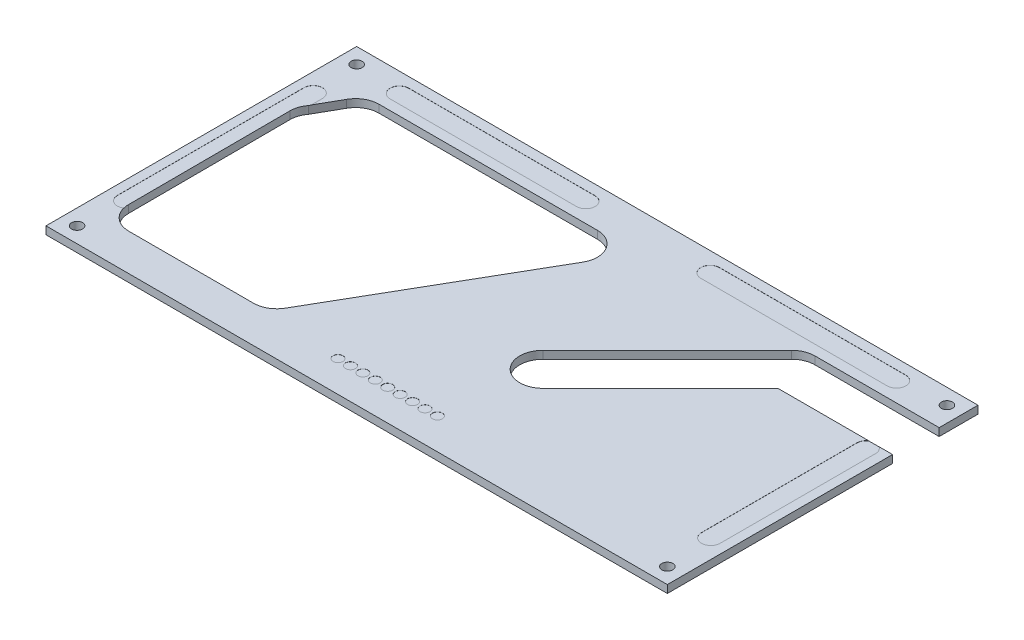
SolidWorks part; units mm, degrees
ref_plane "Front" through (0, 0, 0) normal (0, 0, 1) x (1, 0, 0)
ref_plane "Top" through (0, 0, 0) normal (0, 1, 0) x (1, 0, 0)
ref_plane "Right" through (0, 0, 0) normal (1, 0, 0) x (0, 0, -1)
sketch "Sketch1" plane through (0, 0, 0) normal (0, 1, 0) x (1, 0, 0)
  line L1 (0, 0) -> (127, 0)
  line L2 (0, 0) -> (0, 63.5)
  line L3 (0, 63.5) -> (127, 63.5)
  line L4 (127, 0) -> (127, 63.5)
  dimension "D1" = 63.5
  dimension "D2" = 127
extrude "Boss-Extrude1" add sketch "Sketch1" along normal blind 1.5875
sketch "Sketch2" plane through (0, 1.5875, 0) normal (0, 1, 0) x (1, 0, 0)
  line L0 (0, 63.5) -> (0, 0) construction
  line L1 (127, 63.5) -> (0, 63.5) construction
  line L2 (63.5, 63.5) -> (63.5, 0) construction
  line L3 (0, 0) -> (127, 0) construction
  circle A0 centre (3.175, 60.325) radius 1.1303
  circle A1 centre (3.175, 3.175) radius 1.1303
  circle A2 centre (123.825, 3.175) radius 1.1303
  circle A3 centre (123.825, 60.325) radius 1.1303
  dimension "D1" = 2.2606
  dimension "D2" = 3.175
  dimension "D3" = 3.175
  dimension "D4" = 2
extrude "Cut-Extrude1" cut sketch "Sketch2" against normal through all
sketch "Sketch3" plane through (0, 1.5875, 0) normal (0, 1, 0) x (1, 0, 0)
  line L0 (63.5, 63.5) -> (63.5, 0) construction
  line L1 (127, 63.5) -> (0, 63.5) construction
  line L2 (0, 0) -> (127, 0) construction
  line L3 (3.81, 50.8) -> (3.81, 12.7) construction
  line L4 (5.715, 50.8) -> (5.715, 12.7)
  line L5 (1.905, 50.8) -> (1.905, 12.7)
  line L6 (50.8, 59.5399) -> (12.7, 59.5399) construction
  line L7 (50.8, 57.6349) -> (12.7, 57.6349)
  line L8 (50.8, 61.4449) -> (12.7, 61.4449)
  line L9 (76.2, 59.5399) -> (114.3, 59.5399) construction
  line L10 (76.2, 57.6349) -> (114.3, 57.6349)
  line L11 (76.2, 61.4449) -> (114.3, 61.4449)
  line L12 (123.19, 44.45) -> (123.19, 12.7) construction
  line L13 (125.095, 44.45) -> (125.095, 12.7)
  line L14 (121.285, 44.45) -> (121.285, 12.7)
  circle A0 centre (63.5, 6.35) radius 1.016
  circle A1 centre (66.04, 6.35) radius 1.016
  circle A2 centre (68.58, 6.35) radius 1.016
  circle A3 centre (71.12, 6.35) radius 1.016
  circle A4 centre (73.66, 6.35) radius 1.016
  circle A5 centre (60.96, 6.35) radius 1.016
  circle A6 centre (58.42, 6.35) radius 1.016
  circle A7 centre (55.88, 6.35) radius 1.016
  circle A8 centre (53.34, 6.35) radius 1.016
  arc A9 (5.715, 50.8) -> (1.905, 50.8) centre (3.81, 50.8) ccw
  arc A10 (1.905, 12.7) -> (5.715, 12.7) centre (3.81, 12.7) ccw
  arc A11 (50.8, 57.6349) -> (50.8, 61.4449) centre (50.8, 59.5399) ccw
  arc A12 (12.7, 61.4449) -> (12.7, 57.6349) centre (12.7, 59.5399) ccw
  arc A13 (76.2, 57.6349) -> (76.2, 61.4449) centre (76.2, 59.5399) cw
  arc A14 (114.3, 61.4449) -> (114.3, 57.6349) centre (114.3, 59.5399) cw
  arc A15 (125.095, 44.45) -> (121.285, 44.45) centre (123.19, 44.45) ccw
  arc A16 (121.285, 12.7) -> (125.095, 12.7) centre (123.19, 12.7) ccw
  point P26 (3.81, 31.75)
  point P33 (31.75, 59.5399)
  point P40 (95.25, 59.5399)
  point P47 (123.19, 28.575)
  dimension "D2" = 2.032
  dimension "D1" = 57.15
  dimension "D5" = 3.81
  dimension "D6" = 59.69
  dimension "D7" = 12.7
  dimension "D8" = 38.1
  dimension "D9" = 3.81
  dimension "D10" = 38.1
  dimension "D11" = 50.8
  dimension "D12" = 3.81
  dimension "D13" = 59.69
  dimension "D14" = 31.75
  dimension "D15" = 19.05
  dimension "D3" = 5
  dimension "D4" = 5
sketch "Sketch4" plane through (0, 1.5875, 0) normal (0, 1, 0) x (1, 0, 0)
  line L0 (76.2, 25.4) -> (101.6, 50.8) construction
  line L1 (72.8324, 28.7676) -> (98.2324, 54.1676)
  line L2 (79.5676, 22.0324) -> (104.9676, 47.4324)
  line L3 (0, 0) -> (127, 0) construction
  line L4 (63.5, 63.5) -> (63.5, 0) construction
  line L5 (101.6, 50.8) -> (127, 50.8) construction
  line L6 (127, 0) -> (127, 63.5) construction
  line L7 (101.6, 55.5625) -> (127, 55.5625)
  line L8 (101.6, 46.0375) -> (127, 46.0375)
  arc A0 (72.8324, 28.7676) -> (79.5676, 22.0324) centre (76.2, 25.4) ccw
  arc A1 (104.9676, 47.4324) -> (98.2324, 54.1676) centre (101.6, 50.8) ccw
  arc A2 (101.6, 55.5625) -> (101.6, 46.0375) centre (101.6, 50.8) ccw
  arc A3 (127, 46.0375) -> (127, 55.5625) centre (127, 50.8) ccw
  point P2 (88.9, 38.1)
  point P11 (114.3, 50.8)
  line M15 (127, 0) -> (127, 63.5)
  dimension "D1" = 25.4
  dimension "D2" = 12.7
  dimension "D3" = 38.1
  dimension "D4" = 50.8
  dimension "D5" = 9.525
  dimension "D6" = 9.525
extrude "Cut-Extrude2" cut sketch "Sketch4" against normal blind 1.5875 contours A2 L1 A0 L2 L8 | A1 A2 L8 L2 | A1 L2 L8 L7 M15 region at (86.2305, 1.5875, -35.4396) region at (101.6126, 1.5875, -50.7696) region at (116.1742, 1.5875, -50.8106)
sketch "Sketch5" plane through (0, 1.5875, 0) normal (0, 1, 0) x (-1, 0, 0)
  line L0 (-9.4127, -112.4413) -> (-9.4127, -117.0133) construction
  line L1 (-9.4127, -117.0133) -> (-7.1267, -114.7273) construction
  line L2 (-7.1267, -114.7273) -> (-11.6987, -114.7273) construction
  line L3 (-39.0307, -117.1085) -> (-61.2744, -78.5813)
  line L4 (-57.15, -71.4375) -> (-12.4895, -71.4375)
  line L5 (-34.9063, -119.4898) -> (-9.4127, -119.4898)
  line L6 (-8.317, -73.904) -> (-5.4991, -78.85)
  line L7 (-4.6502, -114.7418) -> (-4.5493, -81.7184)
  line L9 (-63.5, -63.5) -> (-63.5, 0) construction
  line L10 (-127, -63.5) -> (0, -63.5) construction
  line L11 (-7.1267, -12.2727) -> (-11.6987, -12.2727) construction
  line L12 (-9.4127, -9.9867) -> (-7.1267, -12.2727) construction
  line L13 (-9.4127, -14.5587) -> (-9.4127, -9.9867) construction
  line L14 (-4.6502, -12.2582) -> (-4.5493, -45.2816)
  line L15 (-8.317, -53.096) -> (-5.4991, -48.15)
  line L16 (-34.9063, -7.5102) -> (-9.4127, -7.5102)
  line L17 (-57.15, -55.5625) -> (-12.4895, -55.5625)
  line L18 (-39.0307, -9.8915) -> (-61.2744, -48.4187)
  circle A0 centre (-57.15, -76.2) radius 4.7625
  circle A1 centre (-34.9063, -114.7273) radius 4.7625
  circle A2 centre (-12.4895, -76.2) radius 4.7625
  circle A3 centre (-9.3118, -45.2961) radius 4.7625
  circle A4 centre (-9.4127, -114.7273) radius 4.7625
  circle A5 centre (-9.3118, -81.7039) radius 4.7625
  circle A6 centre (-9.4127, -12.2727) radius 4.7625
  circle A7 centre (-12.4895, -50.8) radius 4.7625
  circle A8 centre (-34.9063, -12.2727) radius 4.7625
  circle A9 centre (-57.15, -50.8) radius 4.7625
  dimension "D1" = 9.525
  dimension "D2" = 9.525
  dimension "D3" = 9.525
  dimension "D4" = 9.525
  dimension "D5" = 9.525
  dimension "D6" = 6.35
  dimension "D7" = 12.7
extrude "Cut-Extrude3" cut sketch "Sketch5" against normal blind 1.5875 contours A3 A7 | A7 A3 | A9 | A8 | A6 | A7 A3 | A3 A7 L15 | L18 A9 L17 A7 A3 L14 A6 L16 A8 region at (9.4127, 1.5875, -12.2727) region at (29.4737, 1.5875, -33.6088) region at (8.8674, 1.5875, -44.5264) region at (34.9063, 1.5875, -12.2727) region at (10.9006, 1.5875, -48.0481) region at (12.9339, 1.5875, -51.5697) region at (7.1148, 1.5875, -50.2748) region at (57.15, 1.5875, -50.8)
extrude "Cut-Extrude4" cut sketch "Sketch3" against normal blind 0.0254
